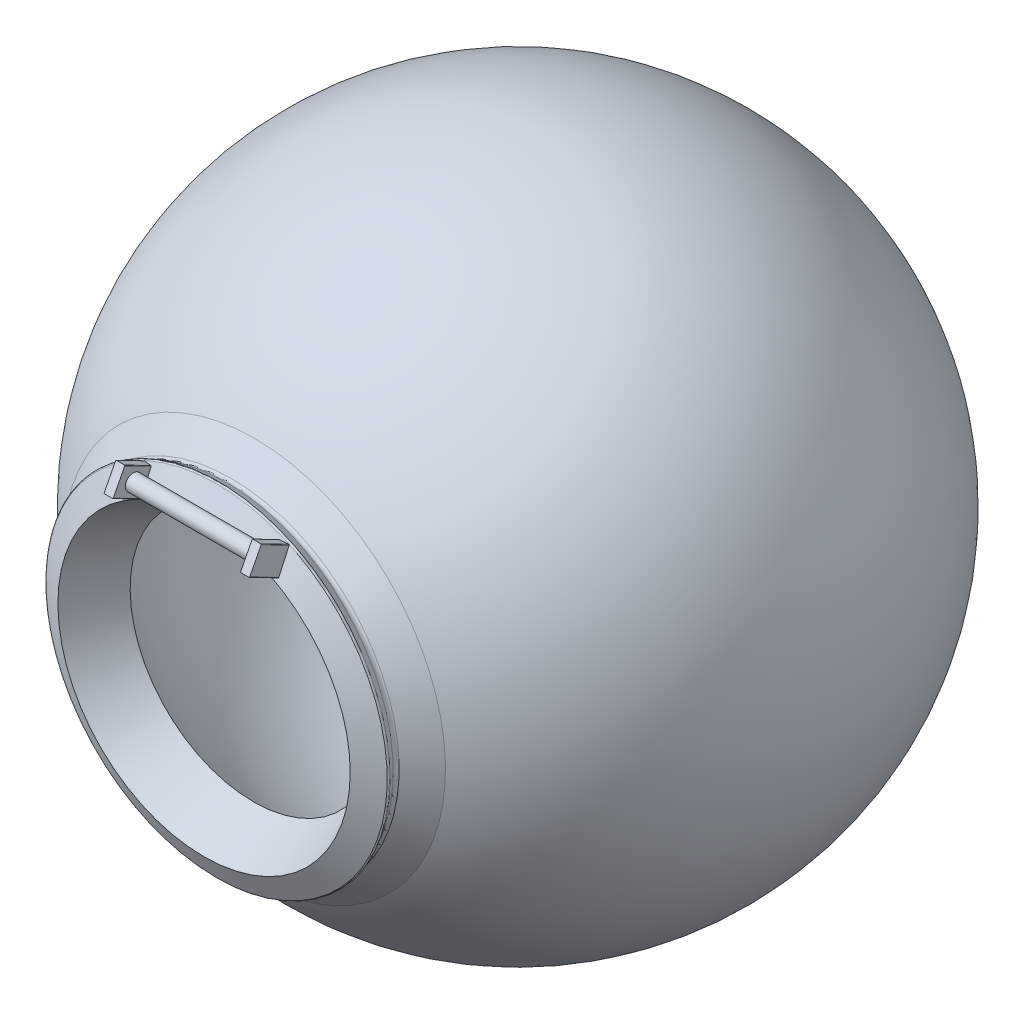
SolidWorks part; units mm, degrees
ref_plane "Front Plane" through (0, 0, 0) normal (0, 0, 1) x (1, 0, 0)
ref_plane "Top Plane" through (0, 0, 0) normal (0, 1, 0) x (1, 0, 0)
ref_plane "Right Plane" through (0, 0, 0) normal (1, 0, 0) x (0, 0, -1)
sketch "Sphere Sketch" plane through (0, 0, 0) normal (1, 0, 0) x (0, 0, -1)
  line L0 (-495, 0) -> (0, 0) construction
  line L1 (-495, 230.6517) -> (0, 0) construction
  line L2 (-495, 230.6517) -> (-495, 0) construction
  line L3 (-587.2743, 273.6481) -> (-495, 230.6517)
  line L5 (0, 0) -> (531.6016, 0) construction
  line L8 (-574.9857, 296.2531) -> (0, 0) construction
  line L9 (-856.9957, 1420.5972) -> (-601.6623, 1420.5972) construction
  line L11 (-563.7113, 319.3806) -> (-587.2743, 273.6481)
  line L12 (-493.3391, 358.0903) -> (-536.2291, 314.1571)
  line L13 (531.6016, 125) -> (531.6016, 0) construction
  line L14 (0, 0) -> (531.6016, 125) construction
  line L15 (-559.553, 320.6095) -> (-545.9307, 312.8043)
  line L16 (-545.9307, 312.8043) -> (0, 0) construction
  line L17 (531.6016, 125) -> (618.1413, 145.3488)
  line L19 (618.1413, 145.3488) -> (568.3844, 220.3438)
  line L20 (-541.9535, 319.7456) -> (-545.9307, 312.8043) construction
  arc A2 (531.6016, 125) -> (-495, 230.6517) centre (0, 0) ccw
  arc A3 (-563.5933, 319.5888) -> (-587.2743, 273.6481) centre (0, 0) ccw construction
  arc A4 (568.3844, 220.3438) -> (-493.3391, 358.0903) centre (0, 0) ccw
  arc A5 (-536.2291, 314.1571) -> (-545.9307, 312.8043) centre (-541.9535, 319.7456) cw
  arc A7 (-563.7113, 319.3806) -> (-559.553, 320.6095) centre (-561.0445, 318.0066) cw
  point P6 (582.4534, 136.9572)
  point P17 (0, 0)
  point P18 (0, 0)
  point P19 (0, 0)
  point P20 (0, 0)
  point P24 (-493.3391, 358.0903)
  point P27 (0, 0)
  point P29 (0, 0)
  dimension "D1" = 495
  dimension "D2" = 609.6
  dimension "D3" = 546.1
  dimension "D4" = 647.9
  dimension "D6" = 15.7
  dimension "D8" = 8
  dimension "D9" = 104.5
  dimension "D10" = 125
  dimension "D11" = 635
  dimension "D5" = 3
  dimension "D7" = 51.4458
  dimension "D12" = 90
revolve "Sphere" add sketch "Sphere Sketch" angle 360 about L5 region at (0, 290.5639, 563.9438)
ref_plane "Hinge Plane" through (0, 296.5144, 575.4928) normal (0, 0.458, 0.8889) x (1, 0, 0)
sketch "Sketch1" plane through (0, 296.5144, 575.4928) normal (0, 0.458, 0.8889) x (1, 0, 0)
  line L0 (0, -25.7229) -> (127.7521, -25.7229) construction
  line L1 (0, 60.5405) -> (0, -60.5405) construction
  line L7 (120.2521, -50.0365) -> (135.2521, -50.0365)
  line L8 (0, -226.7177) -> (0, 0) construction
  line L13 (119.2521, -49.0365) -> (119.2521, -2.4094)
  line L14 (120.2521, -1.4094) -> (135.2521, -1.4094)
  line L15 (136.2521, -49.0365) -> (136.2521, -2.4094)
  line L16 (119.2521, -50.0365) -> (136.2521, -1.4094) construction
  line L17 (119.2521, -1.4094) -> (136.2521, -50.0365) construction
  line L21 (-120.2521, -1.4094) -> (-135.2521, -1.4094)
  line L22 (-136.2521, -49.0365) -> (-136.2521, -2.4094)
  line L23 (-120.2521, -50.0365) -> (-135.2521, -50.0365)
  line L24 (-119.2521, -49.0365) -> (-119.2521, -2.4094)
  arc A4 (136.2521, -2.4094) -> (135.2521, -1.4094) centre (135.2521, -2.4094) ccw
  arc A5 (120.2521, -1.4094) -> (119.2521, -2.4094) centre (120.2521, -2.4094) ccw
  arc A6 (119.2521, -49.0365) -> (120.2521, -50.0365) centre (120.2521, -49.0365) ccw
  arc A10 (136.2521, -49.0365) -> (135.2521, -50.0365) centre (135.2521, -49.0365) cw
  arc A11 (-136.2521, -2.4094) -> (-135.2521, -1.4094) centre (-135.2521, -2.4094) cw
  arc A12 (-136.2521, -49.0365) -> (-135.2521, -50.0365) centre (-135.2521, -49.0365) ccw
  arc A13 (-120.2521, -1.4094) -> (-119.2521, -2.4094) centre (-120.2521, -2.4094) cw
  arc A14 (-119.2521, -49.0365) -> (-120.2521, -50.0365) centre (-120.2521, -49.0365) cw
  ellipse E2 centre (0, -258.1886) end of major axis (-319.3806, -258.1886) minor radius 283.9115 construction
  ellipse E4 centre (0, -268.9808) end of major axis (-273.6481, -268.9808) minor radius 243.2579 construction
  point P5 (127.7521, -25.7229)
  point P17 (0, 0)
  dimension "D1" = 1
  dimension "D2" = 1
  dimension "D4" = 15
extrude "Boss-Extrude3" add sketch "Sketch1" against normal up to surface and the other way blind 15 from offset 30 up to face at (0, -273.6481, 587.2743)
sketch "Sketch3" plane through (136.2521, 0, 0) normal (1, 0, 0) x (0, 0, -1)
  line L0 (-616.5988, 314.9833) -> (-583.5911, 245.5243) construction
  line L1 (-637.9548, 273.5344) -> (-583.5911, 245.5243) construction
  line L2 (-564.1339, 287.9515) -> (-637.9548, 273.5344) construction
  line L3 (-616.5988, 314.9833) -> (-564.1339, 287.9515) construction
  circle A0 centre (-600.3883, 280.8711) radius 15
  spline S0 degree 3 poles (-583.5911, 245.5243) (-577.1994, 259.7119) (-570.702, 273.8487) (-564.1339, 287.9515) knots 0 0 0 0 1 1 1 1 construction
  point P12 (-600.3883, 280.8711)
  dimension "D1" = 30
extrude "Boss-Extrude5" add sketch "Sketch3" against normal up to surface (272.5041 mm away) up to face at (-136.2521, 285.8018, 598.1375)
